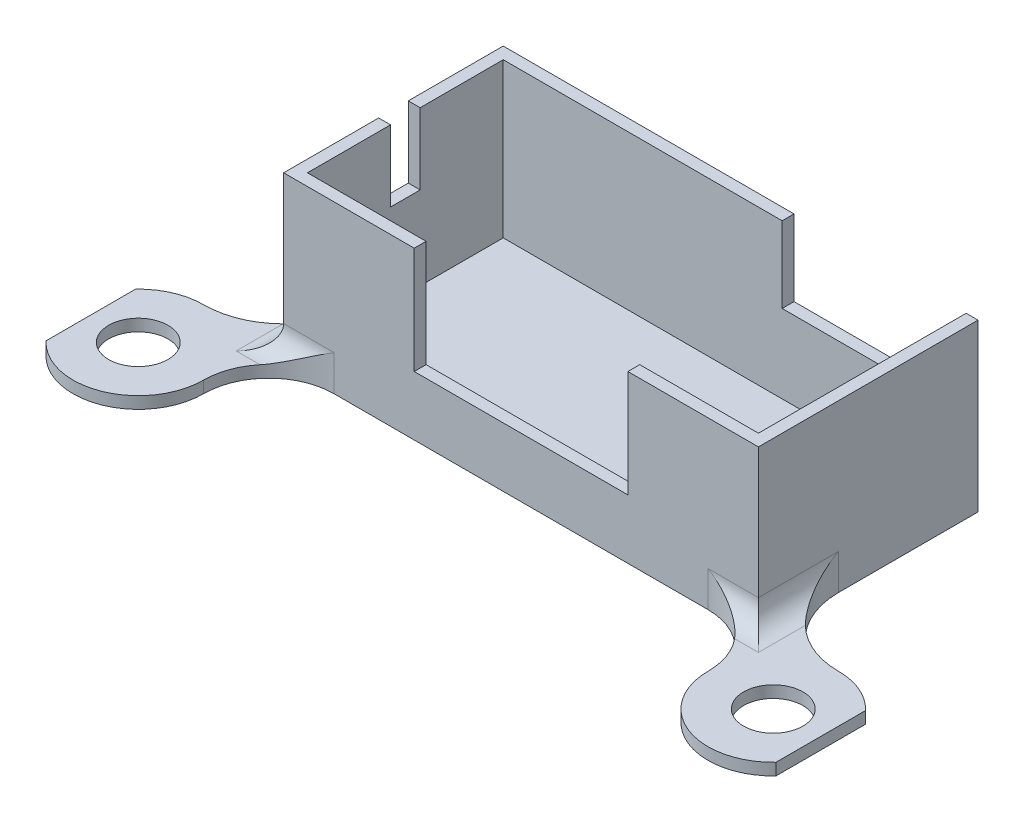
SolidWorks part; units mm, degrees
ref_plane "Front Plane" through (0, 0, 0) normal (0, 0, 1) x (1, 0, 0)
ref_plane "Top Plane" through (0, 0, 0) normal (0, 1, 0) x (1, 0, 0)
ref_plane "Right Plane" through (0, 0, 0) normal (1, 0, 0) x (0, 0, -1)
sketch "Sketch1" plane through (0, 0, 0) normal (0, 1, 0) x (1, 0, 0)
  line L0 (-8.5526, 0) -> (13.4211, 0) construction
  line L1 (0, 9.6227) -> (0, -6.4776) construction
  line L2 (-13.375, 2.75) -> (13.375, 2.75) construction
  line L3 (-10, 12) -> (10, 12)
  line L4 (-10, 12) -> (-10, 2.75)
  line L5 (-10, 2.75) -> (10, 2.75)
  line L6 (10, 12) -> (10, 2.75)
  line L7 (-10, 12) -> (10, 2.75) construction
  line L8 (-10, 2.75) -> (10, 12) construction
  line L9 (-10.625, 0) -> (10.625, 0) construction
  line L10 (-15.375, -1.8875) -> (-15.375, 1.8875)
  line L11 (15.375, -1.8875) -> (15.375, 1.8875)
  circle A0 centre (-13.375, 0) radius 1.25
  circle A1 centre (-13.375, 0) radius 2.75
  circle A2 centre (13.375, 0) radius 2.75
  circle A3 centre (13.375, 0) radius 1.25
  arc A4 (-10.625, 0) -> (-7.875, 2.75) centre (-7.875, 0) cw
  arc A5 (10.625, 0) -> (7.875, 2.75) centre (7.875, 0) ccw
  arc A6 (-13.375, 2.75) -> (-10, 6.125) centre (-13.375, 6.125) ccw
  arc A7 (13.375, 2.75) -> (10, 6.125) centre (13.375, 6.125) cw
  point P0 (0, 0)
  point P12 (0, 7.375)
  dimension "D1" = 2.5
  dimension "D2" = 1.5
  dimension "D3" = 26.75
  dimension "D4" = 20
  dimension "D5" = 9.25
  dimension "D6" = 2
extrude "Boss-Extrude1" add sketch "Sketch1" along normal blind 0.5 contours A1 A0 | L5 A1 | A1 A4 L5 | L6 L3 L4 L5 | L5 A2 | A2 A3 | A5 A2 L5 region at (0, 0, -7.375) region at (-10.6804, 0, -2.7235) region at (10.6804, 0, -2.7235) region at (-11.4818, 0, -1.8932) region at (14.4353, 0, -2.4584)
sketch "Sketch2" plane through (0, 0.5, 0) normal (0, 1, 0) x (1, 0, 0)
  line L0 (-10, 2.75) -> (10, 2.75) construction
  line L1 (-10, 12) -> (-10, 6.125) construction
  line L2 (10, 12) -> (10, 6.125) construction
  line L3 (-7.875, 2.75) -> (7.875, 2.75) construction
  line L4 (-10, 2.75) -> (10, 12) construction
  line L5 (-9.5, 11.5) -> (-10, 11.5) construction
  line L6 (10, 2.75) -> (-10, 2.75)
  line L7 (10, 2.75) -> (10, 12)
  line L8 (10, 12) -> (-10, 12)
  line L9 (-10, 2.75) -> (-10, 12)
  line L10 (10, 2.75) -> (-10, 12) construction
  line L11 (10, 12) -> (-10, 2.75) construction
  line L12 (9.5, 3.25) -> (-9.5, 3.25)
  line L13 (9.5, 3.25) -> (9.5, 11.5)
  line L14 (9.5, 11.5) -> (-9.5, 11.5)
  line L15 (-9.5, 3.25) -> (-9.5, 11.5)
  line L16 (9.5, 3.25) -> (-9.5, 11.5) construction
  line L17 (9.5, 11.5) -> (-9.5, 3.25) construction
  line L18 (-9.5, 11.5) -> (-9.5, 12) construction
  point P10 (0, 7.375)
  point P12 (0, 7.375)
  dimension "D1" = 0.5
extrude "Boss-Extrude2" add sketch "Sketch2" along normal blind 6.5
sketch "Sketch3" plane through (0, 0, -12) normal (0, 0, -1) x (-1, 0, 0)
  line L0 (-10, 7) -> (10, 7) construction
  line L1 (-9.5, 7) -> (-2.25, 7)
  line L2 (-9.5, 7) -> (-9.5, 3.8)
  line L3 (-9.5, 3.8) -> (-2.25, 3.8)
  line L4 (-2.25, 7) -> (-2.25, 3.8)
  line L6 (-10, 0) -> (10, 7) construction
  line L7 (9.5, 7) -> (9.5, 0.5) construction
  line L8 (-9.5, 0.5) -> (9.5, 0.5)
  line L9 (-9.5, 0.5) -> (-9.5, 6.5)
  line L10 (-9.5, 6.5) -> (9.5, 6.5)
  line L11 (9.5, 0.5) -> (9.5, 6.5)
  line L12 (-9.5, 0.5) -> (9.5, 6.5) construction
  line L13 (-9.5, 6.5) -> (9.5, 0.5) construction
  line L14 (9.5, 0.5) -> (-9.5, 0.5) construction
  point P10 (0, 3.5)
  line M8 (10, 7) -> (-10, 7)
  dimension "D1" = 7.25
  dimension "D2" = 3.3
extrude "Cut-Extrude1" cut sketch "Sketch3" against normal up to next contours L10 L2 L3 L4 | L2 L10 L4 M8 region at (5.875, 6.75, -12) region at (5.875, 5.15, -12)
sketch "Sketch4" plane through (-10, 0, 0) normal (-1, 0, 0) x (0, 0, 1)
  line L0 (-12, 7) -> (-2.75, 7) construction
  line L1 (-8, 7) -> (-6.75, 7)
  line L2 (-8, 7) -> (-8, 4)
  line L3 (-8, 4) -> (-6.75, 4)
  line L4 (-6.75, 7) -> (-6.75, 4)
  line L5 (-7.375, 0) -> (-7.375, 7) construction
  line L7 (-8, 7) -> (-6.75, 4) construction
  line L8 (-11.5, 0.5) -> (-3.25, 0.5) construction
  line L9 (-11.5, 0.5) -> (-3.25, 0.5)
  point P8 (-7.375, 7)
  point P10 (-7.375, 5.5)
  point P13 (0, 0)
  point P14 (-9.0625, 7)
  point P15 (0, 0)
  point P16 (0, 0)
  line M8 (-2.75, 7) -> (-12, 7)
  dimension "D1" = 1.25
  dimension "D2" = 3.5
extrude "Cut-Extrude2" cut sketch "Sketch4" against normal up to next contours L4 L2 L3 M8 region at (-10, 5.5, -7.375)
fillet "Fillet1" radius 1 4 edges at (-10, 0.5, -4.4375) (-8.9375, 0.5, -2.75) (8.9375, 0.5, -2.75) (10, 0.5, -4.4375)
sketch "Sketch5" plane through (0, 0, -2.75) normal (0, 0, 1) x (1, 0, 0)
  line L0 (-7.875, 0) -> (7.875, 0) construction
  line L1 (-10, 7) -> (10, 7)
  line L2 (-10, 7) -> (-10, 0)
  line L3 (-10, 0) -> (10, 0)
  line L4 (10, 7) -> (10, 0)
  line L5 (10, 7) -> (10, 1.5) construction
  line L6 (0, 0) -> (0, 7) construction
  line L7 (-9.5, 0.5) -> (9.5, 0.5) construction
  line L8 (-4.5, 7) -> (4.5, 7)
  line L9 (-4.5, 7) -> (-4.5, 2.5)
  line L10 (-4.5, 2.5) -> (4.5, 2.5)
  line L11 (4.5, 7) -> (4.5, 2.5)
  line L12 (-4.5, 7) -> (4.5, 2.5) construction
  line L13 (-4.5, 2.5) -> (4.5, 7) construction
  line L14 (-9.5, 0.5) -> (9.5, 0.5)
  point P11 (0, 4.75)
  dimension "D1" = 9
  dimension "D2" = 2
extrude "Cut-Extrude3" cut sketch "Sketch5" against normal up to next contours L11 L1 L9 L10 region at (0, 4.75, -2.75)
